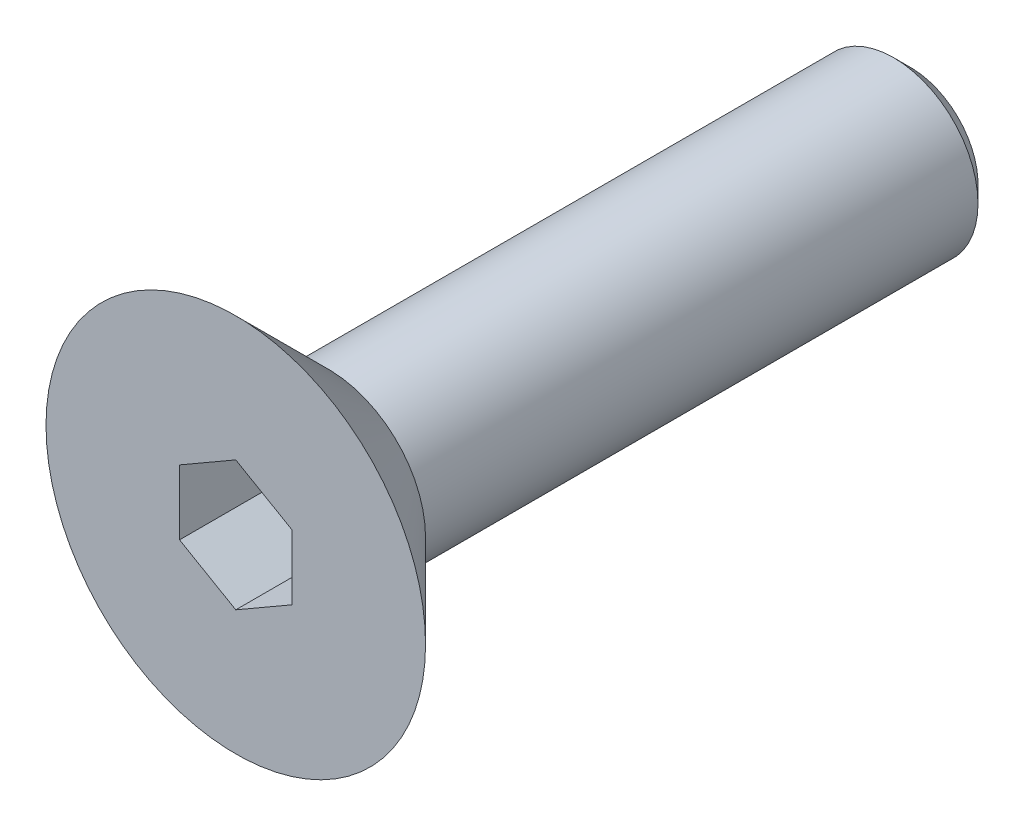
SolidWorks part; units mm, degrees
ref_plane "Front Plane" through (0, 0, 0) normal (0, 0, 1) x (1, 0, 0)
ref_plane "Top Plane" through (0, 0, 0) normal (0, 1, 0) x (1, 0, 0)
ref_plane "Right Plane" through (0, 0, 0) normal (1, 0, 0) x (0, 0, -1)
sketch "Sketch1" plane through (0, 0, 0) normal (0, 0, 1) x (1, 0, 0)
  circle A0 centre (0, 0) radius 3.375
  dimension "D1" = 6.75
extrude "Boss-Extrude1" add sketch "Sketch1" along normal blind 1.65
sketch "Sketch2" plane through (0, 0, 0) normal (0, 0, -1) x (-1, 0, 0)
  circle A0 centre (0, 0) radius 1.5
  dimension "D1" = 3
extrude "Boss-Extrude2" add sketch "Sketch2" along normal blind 10.35
chamfer "Chamfer1" distance 0.3 angle 45 1 edges at (-1.5, 0, -10.35)
sketch "Sketch3" plane through (0, 0, 1.65) normal (0, 0, 1) x (1, 0, 0)
  line L1 (0, 1.1547) -> (-1, 0.5774)
  line L2 (-1, 0.5774) -> (-1, -0.5774)
  line L3 (-1, -0.5774) -> (0, -1.1547)
  line L4 (0, -1.1547) -> (1, -0.5774)
  line L5 (1, -0.5774) -> (1, 0.5774)
  line L6 (1, 0.5774) -> (0, 1.1547)
  circle A0 centre (0, 0) radius 1 construction
  dimension "D1" = 2
extrude "Cut-Extrude1" cut sketch "Sketch3" against normal blind 2
chamfer "Chamfer2" distance 1.65 angle 45 1 edges at (3.375, 0, 0)
